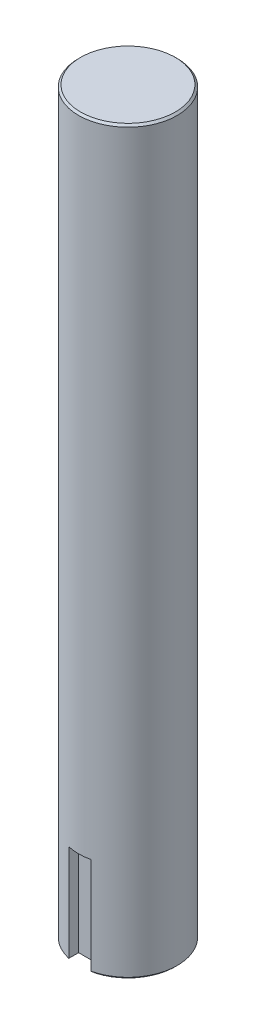
SolidWorks part; units mm, degrees
ref_plane "Front Plane" through (0, 0, 0) normal (0, 0, 1) x (1, 0, 0)
ref_plane "Top Plane" through (0, 0, 0) normal (0, 1, 0) x (1, 0, 0)
ref_plane "Right Plane" through (0, 0, 0) normal (1, 0, 0) x (0, 0, -1)
sketch "Sketch1" plane through (0, 0, 0) normal (0, 0, 1) x (1, 0, 0)
  line L1 (5, 75) -> (0, 75)
  line L2 (5, 75) -> (5, 0)
  line L3 (5, 0) -> (0, 0)
  line L4 (0, 75) -> (0, 0)
  line L5 (5, 75) -> (0, 0) construction
  line L6 (5, 0) -> (0, 75) construction
  point P0 (2.5, 37.5)
  dimension "D1" = 5
  dimension "D2" = 75
revolve "Revolve1" add sketch "Sketch1" angle 360 about L4
sketch "Sketch2" plane through (0, 0, 0) normal (0, -1, 0) x (1, 0, 0)
  line L1 (-1.125, 6.125) -> (1.125, 6.125)
  line L2 (-1.125, 6.125) -> (-1.125, 3.875)
  line L3 (-1.125, 3.875) -> (1.125, 3.875)
  line L4 (1.125, 6.125) -> (1.125, 3.875)
  line L5 (-1.125, 6.125) -> (1.125, 3.875) construction
  line L6 (-1.125, 3.875) -> (1.125, 6.125) construction
  circle A0 centre (0, 0) radius 5 construction
  point P0 (0, 5)
  dimension "D1" = 2.25
extrude "Cut-Extrude1" cut sketch "Sketch2" against normal blind 10
chamfer "Chamfer1" distance 0.2 angle 45 5 edges at (-5, 75, 0) (-1.125, 0, 4.3734) (0, 0, 3.875) (1.125, 0, 4.3734) (0, 0, -5)
ref_axis "Axis1" through (0, 0.2, 0) along (0, 1, 0)
